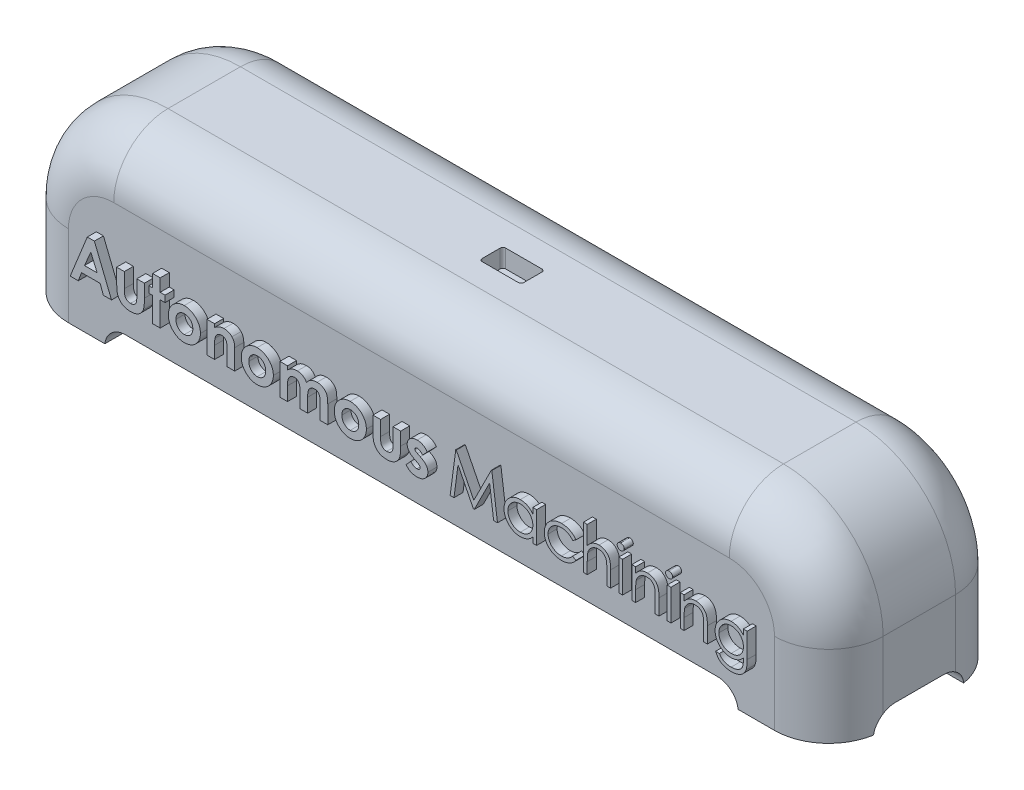
SolidWorks part; units mm, degrees
ref_plane "Front Plane" through (0, 0, 0) normal (0, 0, 1) x (1, 0, 0)
ref_plane "Top Plane" through (0, 0, 0) normal (0, 1, 0) x (1, 0, 0)
ref_plane "Right Plane" through (0, 0, 0) normal (1, 0, 0) x (0, 0, -1)
sketch "Sketch1" plane through (0, 0, 0) normal (0, 1, 0) x (1, 0, 0)
  line L1 (-114.3, 25.4) -> (114.3, 25.4)
  line L2 (-114.3, 25.4) -> (-114.3, -25.4)
  line L3 (-114.3, -25.4) -> (114.3, -25.4)
  line L4 (114.3, 25.4) -> (114.3, -25.4)
  line L5 (-114.3, 25.4) -> (114.3, -25.4) construction
  line L6 (-114.3, -25.4) -> (114.3, 25.4) construction
  point P0 (0, 0)
  dimension "D1" = 50.8
  dimension "D2" = 228.6
extrude "Boss-Extrude1" add sketch "Sketch1" along normal blind 50.8
sketch "Sketch2" plane through (0, 50.8, 0) normal (0, 1, 0) x (1, 0, 0)
  line L1 (-5.08, 3.302) -> (5.08, 3.302)
  line L2 (-5.842, 2.54) -> (-5.842, -2.54)
  line L3 (-5.08, -3.302) -> (5.08, -3.302)
  line L4 (5.842, 2.54) -> (5.842, -2.54)
  line L5 (-5.842, 3.302) -> (5.842, -3.302) construction
  line L6 (-5.842, -3.302) -> (5.842, 3.302) construction
  line L7 (-62.23, 7.62) -> (62.23, 7.62)
  line L8 (-62.23, 7.62) -> (-62.23, -7.62)
  line L9 (-62.23, -7.62) -> (62.23, -7.62)
  line L10 (62.23, 7.62) -> (62.23, -7.62)
  line L11 (-62.23, 7.62) -> (62.23, -7.62) construction
  line L12 (-62.23, -7.62) -> (62.23, 7.62) construction
  arc A0 (-5.842, -2.54) -> (-5.08, -3.302) centre (-5.08, -2.54) ccw
  arc A1 (5.08, -3.302) -> (5.842, -2.54) centre (5.08, -2.54) ccw
  arc A2 (5.08, 3.302) -> (5.842, 2.54) centre (5.08, 2.54) cw
  arc A3 (-5.08, 3.302) -> (-5.842, 2.54) centre (-5.08, 2.54) ccw
  point P0 (0, 0)
  point P6 (0, 0)
  dimension "D5" = 0.762
  dimension "D1" = 11.684
  dimension "D2" = 6.604
  dimension "D3" = 124.46
  dimension "D4" = 15.24
extrude "Cut-Extrude1" cut sketch "Sketch2" against normal blind 5.08 contours L4 L1 L2 L3 region at (0, 50.8, 0)
fillet "Fillet1" radius 27.94 2 edges at (114.3, 50.8, 0) (-114.3, 50.8, 0)
fillet "Fillet2" radius 15.24 10 edges at (114.3, 11.43, -25.4) (106.1166, 42.6166, -25.4) (-114.3, 11.43, -25.4) (-106.1166, 42.6166, -25.4) (-114.3, 11.43, 25.4) (-106.1166, 42.6166, 25.4) (114.3, 11.43, 25.4) (106.1166, 42.6166, 25.4) (0, 50.8, -25.4) (0, 50.8, 25.4)
sketch "Sketch3" plane through (0, 0, 25.4) normal (0, 0, 1) x (1, 0, 0)
  text T0 "<b>Autonomous </b>Machining" font "Century Gothic" height in points 45
extrude "Boss-Extrude2" add sketch "Sketch3" along normal blind 2.54
sketch "Sketch4" plane through (0, 0, 0) normal (0, -1, 0) x (1, 0, 0)
  line L1 (-95.758, 15.24) -> (95.758, 15.24)
  line L2 (-101.6, 9.398) -> (-101.6, -9.398)
  line L3 (-95.758, -15.24) -> (95.758, -15.24)
  line L4 (-99.06, -25.4) -> (99.06, -25.4)
  line L5 (114.3, -10.16) -> (114.3, 10.16)
  line L6 (99.06, 25.4) -> (-99.06, 25.4)
  line L7 (-114.3, 10.16) -> (-114.3, -10.16)
  line L8 (-99.06, -25.4) -> (99.06, -25.4)
  line L9 (114.3, -10.16) -> (114.3, 10.16)
  line L10 (99.06, 25.4) -> (-99.06, 25.4)
  line L11 (-114.3, 10.16) -> (-114.3, -10.16)
  line L12 (101.6, 9.398) -> (101.6, -9.398)
  line L13 (-101.6, 15.24) -> (101.6, -15.24) construction
  line L14 (-101.6, -15.24) -> (101.6, 15.24) construction
  arc A0 (-101.6, -9.398) -> (-95.758, -15.24) centre (-95.758, -9.398) ccw
  arc A1 (95.758, -15.24) -> (101.6, -9.398) centre (95.758, -9.398) ccw
  arc A2 (95.758, 15.24) -> (101.6, 9.398) centre (95.758, 9.398) cw
  arc A3 (-95.758, 15.24) -> (-101.6, 9.398) centre (-95.758, 9.398) ccw
  arc A4 (99.06, -25.4) -> (114.3, -10.16) centre (99.06, -10.16) ccw
  arc A5 (114.3, 10.16) -> (99.06, 25.4) centre (99.06, 10.16) ccw
  arc A6 (-99.06, 25.4) -> (-114.3, 10.16) centre (-99.06, 10.16) ccw
  arc A7 (-114.3, -10.16) -> (-99.06, -25.4) centre (-99.06, -10.16) ccw
  arc A8 (99.06, -25.4) -> (114.3, -10.16) centre (99.06, -10.16) ccw
  arc A9 (114.3, 10.16) -> (99.06, 25.4) centre (99.06, 10.16) ccw
  arc A10 (-99.06, 25.4) -> (-114.3, 10.16) centre (-99.06, 10.16) ccw
  arc A11 (-114.3, -10.16) -> (-99.06, -25.4) centre (-99.06, -10.16) ccw
  point P2 (0, 0)
  dimension "D4" = 5.842
  dimension "D2" = 203.2
  dimension "D3" = 30.48
  dimension "D1" = 0
extrude "Cut-Extrude2" cut sketch "Sketch4" against normal blind 22.86 contours L2 A0 L3 A1 L12 A2 L1 A3
sketch "Sketch5" plane through (0, 0, 25.4) normal (0, 0, 1) x (1, 0, 0)
  line L1 (-83.058, 5.08) -> (83.058, 5.08)
  line L2 (-88.9, -0.762) -> (-88.9, -5.08)
  line L3 (-88.9, -5.08) -> (88.9, -5.08)
  line L4 (88.9, -0.762) -> (88.9, -5.08)
  line L5 (-88.9, 5.08) -> (88.9, -5.08) construction
  line L6 (-88.9, -5.08) -> (88.9, 5.08) construction
  arc A0 (83.058, 5.08) -> (88.9, -0.762) centre (83.058, -0.762) cw
  arc A1 (-83.058, 5.08) -> (-88.9, -0.762) centre (-83.058, -0.762) ccw
  point P0 (0, 0)
  dimension "D3" = 5.842
  dimension "D1" = 177.8
  dimension "D2" = 10.16
extrude "Cut-Extrude3" cut sketch "Sketch5" against normal through all
ref_axis "Axis1" through (0, 53.594, 0) along (0, -1, 0)
pattern_circular "CirPattern1" count 2 over 360 about axis through (0, 53.594, 0) along (0, -1, 0) of "Boss-Extrude2"
sketch "Sketch6" plane through (114.3, 0, 0) normal (1, 0, 0) x (0, 0, -1)
  line L1 (-6.858, 5.08) -> (6.858, 5.08)
  line L2 (-12.7, -0.762) -> (-12.7, -5.08)
  line L3 (-12.7, -5.08) -> (12.7, -5.08)
  line L4 (12.7, -0.762) -> (12.7, -5.08)
  line L5 (-12.7, 5.08) -> (12.7, -5.08) construction
  line L6 (-12.7, -5.08) -> (12.7, 5.08) construction
  arc A0 (6.858, 5.08) -> (12.7, -0.762) centre (6.858, -0.762) cw
  arc A1 (-6.858, 5.08) -> (-12.7, -0.762) centre (-6.858, -0.762) ccw
  point P0 (0, 0)
  dimension "D3" = 5.842
  dimension "D1" = 10.16
  dimension "D2" = 25.4
extrude "Cut-Extrude4" cut sketch "Sketch6" against normal through all
